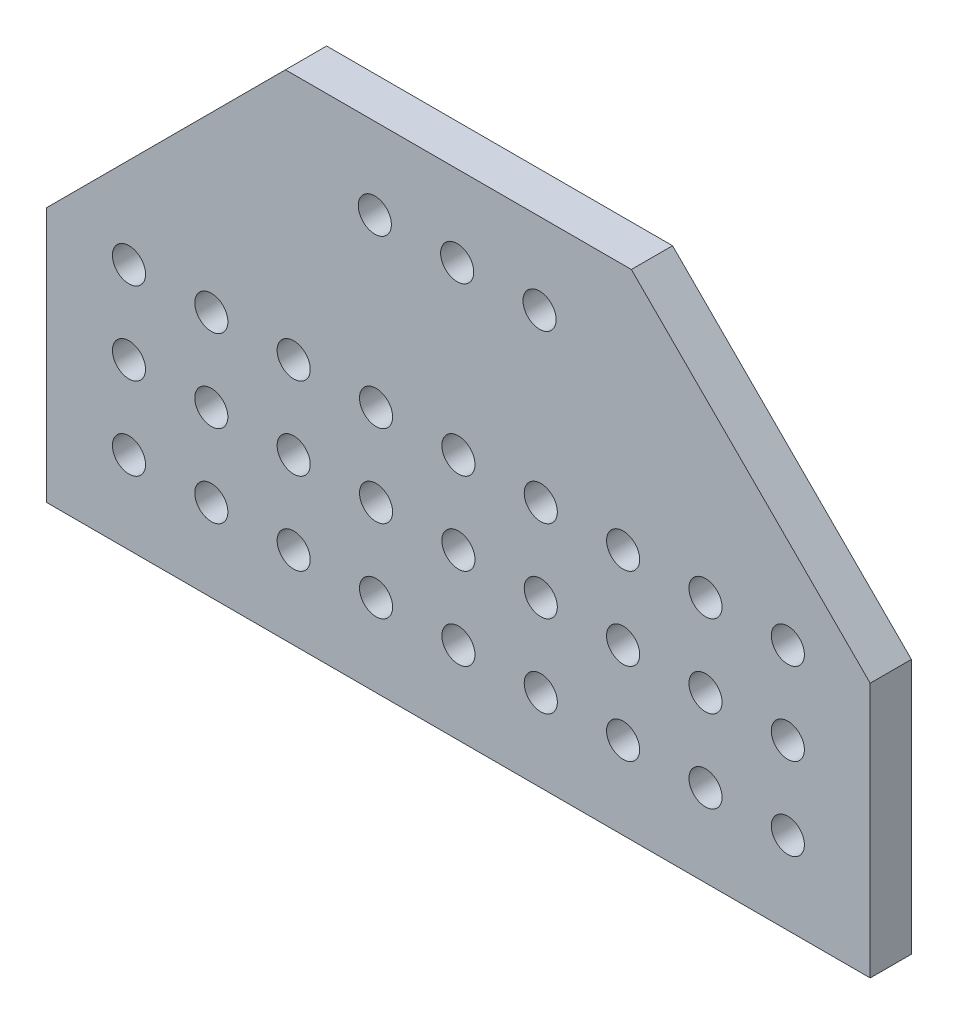
SolidWorks part; units mm, degrees
material "6061-T6 (SS)"
ref_plane "Front Plane" through (0, 0, 0) normal (0, 0, 1) x (1, 0, 0)
ref_plane "Top Plane" through (0, 0, 0) normal (0, 1, 0) x (1, 0, 0)
ref_plane "Right Plane" through (0, 0, 0) normal (1, 0, 0) x (0, 0, -1)
sketch "Sketch1" plane through (0, 0, 0) normal (0, 0, 1) x (1, 0, 0)
  line L1 (0, 0) -> (127, 0)
  line L2 (0, 0) -> (0, 82.55)
  line L3 (0, 82.55) -> (127, 82.55)
  line L4 (127, 0) -> (127, 82.55)
  dimension "D1" = 82.55
  dimension "D2" = 127
extrude "Boss-Extrude1" add sketch "Sketch1" along normal blind 6.35
sketch "Sketch2" plane through (0, 0, 0) normal (0, 0, -1) x (-1, 0, 0)
  line L0 (-127, 82.55) -> (0, 82.55) construction
  line L1 (0, 82.55) -> (0, 0) construction
  circle A0 centre (-76.0095, 63.6905) radius 2.5527
  circle A1 centre (-63.3095, 63.6905) radius 2.5527
  circle A2 centre (-50.6095, 63.6905) radius 2.5527
  dimension "D1" = 18.8595
  dimension "D2" = 12.7
  dimension "D3" = 12.7
  dimension "D4" = 50.6095
  dimension "D5" = 18.8595
  dimension "D6" = 18.8595
  dimension "D7" = 5.1054
  dimension "D8" = 5.1054
  dimension "D9" = 5.1054
extrude "Cut-Extrude1" cut sketch "Sketch2" against normal through all and the other way through all
sketch "Sketch3" plane through (0, 0, 0) normal (0, 0, -1) x (-1, 0, 0)
  line L0 (-127, 0) -> (-127, 82.55) construction
  line L1 (0, 0) -> (-127, 0) construction
  circle A0 centre (-114.3, 38.1) radius 2.5527
  circle A1 centre (-114.3, 25.4) radius 2.5527
  circle A2 centre (-114.3, 12.7) radius 2.5527
  circle A3 centre (-101.6, 38.1) radius 2.5527
  circle A4 centre (-101.6, 25.4) radius 2.5527
  circle A5 centre (-101.6, 12.7) radius 2.5527
  circle A6 centre (-88.9, 38.1) radius 2.5527
  circle A7 centre (-88.9, 25.4) radius 2.5527
  circle A8 centre (-88.9, 12.7) radius 2.5527
  circle A9 centre (-76.2, 38.1) radius 2.5527
  circle A10 centre (-76.2, 25.4) radius 2.5527
  circle A11 centre (-76.2, 12.7) radius 2.5527
  circle A12 centre (-63.5, 38.1) radius 2.5527
  circle A13 centre (-63.5, 25.4) radius 2.5527
  circle A14 centre (-63.5, 12.7) radius 2.5527
  circle A15 centre (-50.8, 38.1) radius 2.5527
  circle A16 centre (-50.8, 25.4) radius 2.5527
  circle A17 centre (-50.8, 12.7) radius 2.5527
  circle A18 centre (-38.1, 38.1) radius 2.5527
  circle A19 centre (-38.1, 25.4) radius 2.5527
  circle A20 centre (-38.1, 12.7) radius 2.5527
  circle A21 centre (-25.4, 38.1) radius 2.5527
  circle A22 centre (-25.4, 25.4) radius 2.5527
  circle A23 centre (-25.4, 12.7) radius 2.5527
  circle A24 centre (-12.7, 38.1) radius 2.5527
  circle A25 centre (-12.7, 25.4) radius 2.5527
  circle A26 centre (-12.7, 12.7) radius 2.5527
  dimension "D1" = 5.1054
  dimension "D2" = 5.1054
  dimension "D3" = 5.1054
  dimension "D4" = 12.7
  dimension "D5" = 12.7
  dimension "D6" = 12.7
  dimension "D7" = 12.7
  dimension "D8" = 12.7
  dimension "D9" = 12.7
  dimension "D11" = 12.7
  dimension "D10" = 9
extrude "Cut-Extrude2" cut sketch "Sketch3" against normal through all
sketch "Sketch4" plane through (0, 0, 0) normal (0, 0, -1) x (-1, 0, 0)
  line L0 (-83.82, 82.55) -> (-127, 39.37)
  line L1 (-127, 82.55) -> (0, 82.55) construction
  line L2 (-127, 39.37) -> (-127, 82.55)
  line L3 (-127, 82.55) -> (-83.82, 82.55)
  line L4 (-43.18, 82.55) -> (0, 82.55)
  line L5 (0, 82.55) -> (0, 39.37)
  line L6 (0, 82.55) -> (0, 0) construction
  line L7 (0, 39.37) -> (-43.18, 82.55)
  dimension "D1" = 45
  dimension "D2" = 45
  dimension "D3" = 43.18
  dimension "D4" = 43.18
extrude "Cut-Extrude3" cut sketch "Sketch4" against normal through all
sketch "Sketch5" plane through (0, 0, 0) normal (0, 0, -1) x (-1, 0, 0)
  line L0 (-90.17, 76.2) -> (-36.83, 76.2)
  line L1 (-127, 39.37) -> (-83.82, 82.55) construction
  line L2 (-43.18, 82.55) -> (0, 39.37) construction
  line L3 (-36.83, 76.2) -> (-43.18, 82.55)
  line L4 (-43.18, 82.55) -> (-83.82, 82.55)
  line L5 (-83.82, 82.55) -> (-90.17, 76.2)
  dimension "D1" = 6.35
extrude "Cut-Extrude4" cut sketch "Sketch5" against normal through all
